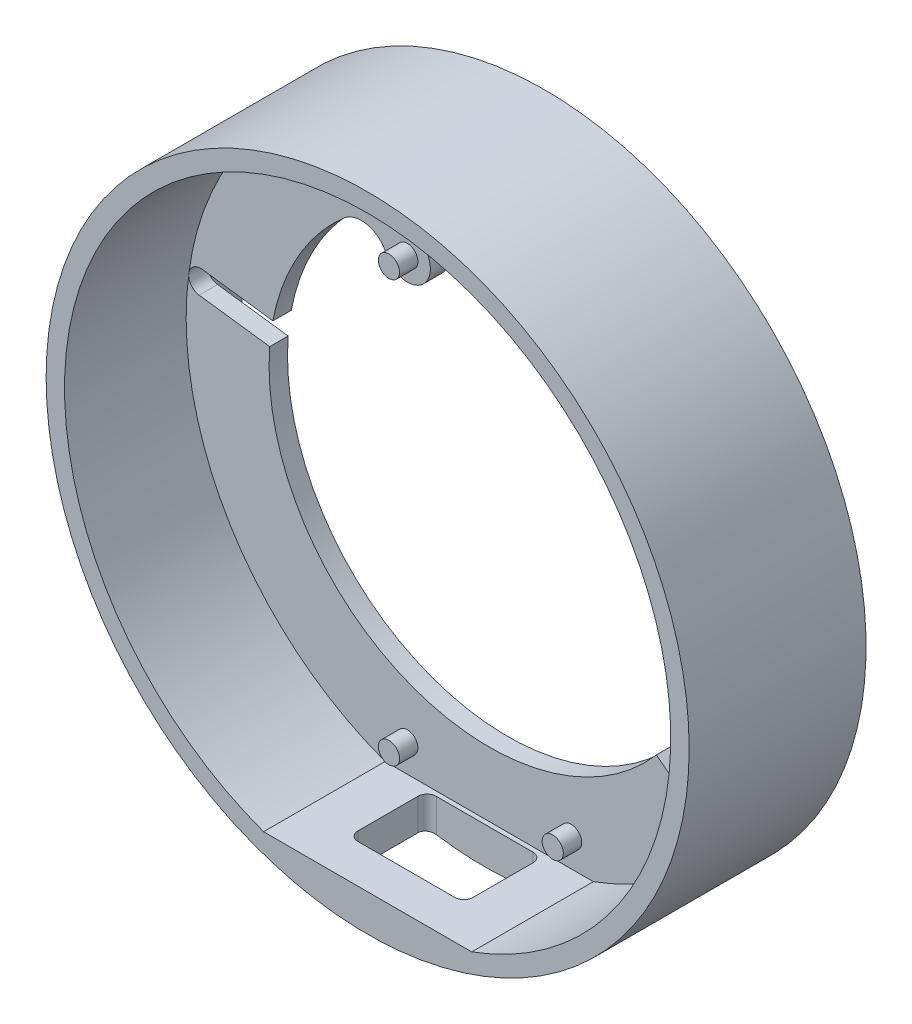
SolidWorks part; units mm, degrees
ref_plane "Plan de face" through (0, 0, 0) normal (0, 0, 1) x (1, 0, 0)
ref_plane "Plan de dessus" through (0, 0, 0) normal (0, 1, 0) x (1, 0, 0)
ref_plane "Plan de droite" through (0, 0, 0) normal (1, 0, 0) x (0, 0, -1)
sketch "Esquisse_carte_affichage" plane through (0, 0, 0) normal (0, 0, 1) x (1, 0, 0)
  circle A0 centre (19.25, 25.1) radius 0.5
  circle A1 centre (25.07, -19.23) radius 0.5
  circle A2 centre (29.18, 12.09) radius 0.5
  circle A3 centre (31.32, -4.14) radius 0.5
  circle A4 centre (-29.21, -12.07) radius 0.5
  circle A5 centre (-31.32, 4.14) radius 0.5
  circle A6 centre (-26.4935, -7.4094) radius 0.25
  circle A7 centre (-23.6728, -14.0139) radius 0.25
  circle A8 centre (-19.2392, -19.6637) radius 0.25
  circle A9 centre (-13.4943, -23.973) radius 0.25
  circle A10 centre (-6.8298, -26.6487) radius 0.25
  circle A11 centre (0.3, -27.5085) radius 0.25
  circle A12 centre (7.4094, -26.4935) radius 0.25
  circle A13 centre (14.0139, -23.6728) radius 0.25
  circle A14 centre (19.6637, -19.2392) radius 0.25
  circle A15 centre (23.973, -13.4943) radius 0.25
  circle A16 centre (26.6487, -6.8298) radius 0.25
  circle A17 centre (27.5085, 0.3) radius 0.25
  circle A18 centre (26.4935, 7.4094) radius 0.25
  circle A19 centre (23.6728, 14.0139) radius 0.25
  circle A20 centre (19.2392, 19.6637) radius 0.25
  circle A21 centre (13.4943, 23.973) radius 0.25
  circle A22 centre (6.8298, 26.6487) radius 0.25
  circle A23 centre (-0.3, 27.5085) radius 0.25
  circle A24 centre (-7.4094, 26.4935) radius 0.25
  circle A25 centre (-14.0139, 23.6728) radius 0.25
  circle A26 centre (-19.6637, 19.2392) radius 0.25
  circle A27 centre (-23.973, 13.4943) radius 0.25
  circle A28 centre (-26.6487, 6.8298) radius 0.25
  circle A29 centre (-27.5085, -0.3) radius 0.25
  circle A30 centre (-30.2, -7.1) radius 0.25
  circle A31 centre (-26.5986, -15.746) radius 0.25
  circle A32 centre (-28.1305, -7.8674) radius 0.25
  circle A33 centre (-21.6169, -22.0937) radius 0.25
  circle A34 centre (-25.1358, -14.8801) radius 0.25
  circle A35 centre (-15.162, -26.9359) radius 0.25
  circle A36 centre (-20.428, -20.8785) radius 0.25
  circle A37 centre (-7.6738, -29.9423) radius 0.25
  circle A38 centre (-14.3281, -25.4544) radius 0.25
  circle A39 centre (0.3371, -30.9082) radius 0.25
  circle A40 centre (-7.252, -28.2956) radius 0.25
  circle A41 centre (8.3254, -29.7678) radius 0.25
  circle A42 centre (0.3185, -29.2082) radius 0.25
  circle A43 centre (15.746, -26.5986) radius 0.25
  circle A44 centre (7.8674, -28.1305) radius 0.25
  circle A45 centre (22.0937, -21.6169) radius 0.25
  circle A46 centre (14.8801, -25.1358) radius 0.25
  circle A47 centre (26.9359, -15.162) radius 0.25
  circle A48 centre (20.8785, -20.428) radius 0.25
  circle A49 centre (29.9423, -7.6738) radius 0.25
  circle A50 centre (25.4544, -14.3281) radius 0.25
  circle A51 centre (30.9082, 0.3371) radius 0.25
  circle A52 centre (28.2956, -7.252) radius 0.25
  circle A53 centre (29.7678, 8.3254) radius 0.25
  circle A54 centre (29.2082, 0.3185) radius 0.25
  circle A55 centre (26.5986, 15.746) radius 0.25
  circle A56 centre (28.1305, 7.8674) radius 0.25
  circle A57 centre (21.6169, 22.0937) radius 0.25
  circle A58 centre (25.1358, 14.8801) radius 0.25
  circle A59 centre (15.162, 26.9359) radius 0.25
  circle A60 centre (20.428, 20.8785) radius 0.25
  circle A61 centre (7.6738, 29.9423) radius 0.25
  circle A62 centre (14.3281, 25.4544) radius 0.25
  circle A63 centre (-0.3371, 30.9082) radius 0.25
  circle A64 centre (7.252, 28.2956) radius 0.25
  circle A65 centre (-8.3254, 29.7678) radius 0.25
  circle A66 centre (-0.3185, 29.2082) radius 0.25
  circle A67 centre (-15.746, 26.5986) radius 0.25
  circle A68 centre (-7.8674, 28.1305) radius 0.25
  circle A69 centre (-22.0937, 21.6169) radius 0.25
  circle A70 centre (-14.8801, 25.1358) radius 0.25
  circle A71 centre (-26.9359, 15.162) radius 0.25
  circle A72 centre (-20.8785, 20.428) radius 0.25
  circle A73 centre (-29.9423, 7.6738) radius 0.25
  circle A74 centre (-25.4544, 14.3281) radius 0.25
  circle A75 centre (-30.9082, -0.3371) radius 0.25
  circle A76 centre (-28.2956, 7.252) radius 0.25
  circle A77 centre (0, 0) radius 26.162
  circle A78 centre (0, 0) radius 32.766
  dimension "D1" = 65.532
  dimension "D2" = 52.324
sketch "Esquisse_carte_mère" plane through (0, 0, 0) normal (0, 0, 1) x (1, 0, 0)
  line L0 (-11.3435, -28.5174) -> (-11.0897, -29.13)
  line L1 (-11.0897, -29.13) -> (-10.6861, -29.6561)
  line L2 (-10.6861, -29.6561) -> (-10.16, -30.0597)
  line L3 (-10.16, -30.0597) -> (-9.5474, -30.3135)
  line L4 (-9.5474, -30.3135) -> (-8.89, -30.4)
  line L5 (-8.89, -30.4) -> (-2.413, -30.4)
  line L6 (-2.413, -30.4) -> (-1.905, -29.892)
  line L7 (-1.905, -29.892) -> (1.905, -29.892)
  line L8 (1.905, -29.892) -> (2.413, -30.4)
  line L9 (2.413, -30.4) -> (8.89, -30.4)
  line L10 (8.89, -30.4) -> (9.5474, -30.3135)
  line L11 (9.5474, -30.3135) -> (10.16, -30.0597)
  line L12 (10.16, -30.0597) -> (10.6861, -29.6561)
  line L13 (10.6861, -29.6561) -> (11.0897, -29.13)
  line L14 (11.0897, -29.13) -> (11.3435, -28.5174)
  line L15 (11.3435, -28.5174) -> (11.43, -27.86)
  line L16 (11.43, -27.86) -> (11.43, 17.86)
  line L17 (11.43, 17.86) -> (11.3435, 18.5174)
  line L18 (11.3435, 18.5174) -> (11.0897, 19.13)
  line L19 (11.0897, 19.13) -> (10.6861, 19.6561)
  line L20 (10.6861, 19.6561) -> (10.16, 20.0597)
  line L21 (10.16, 20.0597) -> (9.5474, 20.3135)
  line L22 (9.5474, 20.3135) -> (8.89, 20.4)
  line L23 (8.89, 20.4) -> (-8.89, 20.4)
  line L24 (-8.89, 20.4) -> (-9.5474, 20.3135)
  line L25 (-9.5474, 20.3135) -> (-10.16, 20.0597)
  line L26 (-10.16, 20.0597) -> (-10.6861, 19.6561)
  line L27 (-10.6861, 19.6561) -> (-11.0897, 19.13)
  line L28 (-11.0897, 19.13) -> (-11.3435, 18.5174)
  line L29 (-11.3435, 18.5174) -> (-11.43, 17.86)
  line L30 (-11.43, 17.86) -> (-11.43, -27.86)
  line L31 (-11.43, -27.86) -> (-11.3435, -28.5174)
  line L32 (8.9522, -28.0199) -> (-18113.3609, 46572.2136) construction
  line L33 (-8.9266, -27.9541) -> (18113.3865, 46572.2795) construction
  circle A0 centre (-3.3, -25.05) radius 0.4
  circle A1 centre (3.3, -25.05) radius 0.4
  circle A2 centre (-3.6, -27.86) radius 0.45
  circle A3 centre (3.6, -27.86) radius 0.45
  circle A4 centre (10.16, 14.05) radius 0.5
  circle A5 centre (10.16, 11.51) radius 0.5
  circle A6 centre (10.16, 8.97) radius 0.5
  circle A7 centre (10.16, 6.43) radius 0.5
  circle A8 centre (10.16, 3.89) radius 0.5
  circle A9 centre (10.16, 1.35) radius 0.5
  circle A10 centre (10.16, -1.19) radius 0.5
  circle A11 centre (10.16, -3.73) radius 0.5
  circle A12 centre (10.16, -6.27) radius 0.5
  circle A13 centre (10.16, -8.81) radius 0.5
  circle A14 centre (10.16, -11.35) radius 0.5
  circle A15 centre (10.16, -13.89) radius 0.5
  circle A16 centre (-10.16, -24.05) radius 0.5
  circle A17 centre (-10.16, -21.51) radius 0.5
  circle A18 centre (-10.16, -18.97) radius 0.5
  circle A19 centre (-10.16, -16.43) radius 0.5
  circle A20 centre (-10.16, -13.89) radius 0.5
  circle A21 centre (-10.16, -11.35) radius 0.5
  circle A22 centre (-10.16, -8.81) radius 0.5
  circle A23 centre (-10.16, -6.27) radius 0.5
  circle A24 centre (-10.16, -3.73) radius 0.5
  circle A25 centre (-10.16, -1.19) radius 0.5
  circle A26 centre (-10.16, 1.35) radius 0.5
  circle A27 centre (-10.16, 3.89) radius 0.5
  circle A28 centre (-10.16, 6.43) radius 0.5
  circle A29 centre (-10.16, 8.97) radius 0.5
  circle A30 centre (-10.16, 11.51) radius 0.5
  circle A31 centre (-10.16, 14.05) radius 0.5
  circle A32 centre (-8.89, -27.86) radius 1.25
  circle A33 centre (8.89, -27.86) radius 1.25
  circle A34 centre (-8.89, 17.86) radius 1.25
  circle A35 centre (8.89, 17.86) radius 1.25
  circle A36 centre (-1.95, -25.955) radius 0.35
  circle A37 centre (1.95, -25.955) radius 0.35
  circle A38 centre (-2.2, 15.706) radius 0.45
  circle A39 centre (3.048, -15.795) radius 0.25
  circle A40 centre (1.016, -20.875) radius 0.25
  circle A41 centre (-6.223, -9.826) radius 0.25
  circle A42 centre (-6.096, -16.43) radius 0.25
  circle A43 centre (7.3914, -2.0028) radius 0.25
  circle A44 centre (7.366, -18.462) radius 0.25
  circle A45 centre (-1.905, 12.018) radius 0.25
  circle A46 centre (1.905, 9.224) radius 0.25
  circle A47 centre (-5.715, -21.129) radius 0.25
  circle A48 centre (-4.064, -1.571) radius 0.25
  circle A49 centre (-8.509, -22.78) radius 0.25
  circle A50 centre (0.2286, -14.5758) radius 0.25
  circle A51 centre (0.508, 7.446) radius 0.25
  circle A52 centre (0.635, 8.589) radius 0.25
  circle A53 centre (-7.112, 0.334) radius 0.25
  circle A54 centre (4.953, -15.795) radius 0.25
  circle A55 centre (0, 10.494) radius 0.25
  circle A56 centre (-4.191, -16.43) radius 0.25
  circle A57 centre (-0.889, -17.573) radius 0.25
  circle A58 centre (5.842, -10.715) radius 0.25
  circle A59 centre (2.159, -17.446) radius 0.25
  circle A60 centre (0, -27.987) radius 0.25
  circle A61 centre (-1.397, 4.271) radius 0.25
  circle A62 centre (-5.207, 1.985) radius 0.25
  circle A63 centre (-0.381, -6.651) radius 0.25
  circle A64 centre (6.858, 8.462) radius 0.25
  circle A65 centre (5.207, 3.128) radius 0.25
  circle A66 centre (2.667, 4.525) radius 0.25
  circle A67 centre (5.08, 11.764) radius 0.25
  circle A68 centre (0, 14.431) radius 0.25
  circle A69 centre (-1.778, 8.716) radius 0.25
  circle A70 centre (-2.921, 4.271) radius 0.25
  circle A71 centre (-5.588, 3.128) radius 0.25
  circle A72 centre (-1.905, -19.732) radius 0.25
  circle A73 centre (-5.842, -8.683) radius 0.25
  circle A74 centre (-3.048, -20.113) radius 0.25
  circle A75 centre (-6.604, -7.667) radius 0.25
  circle A76 centre (-5.207, -10.842) radius 0.25
  circle A77 centre (10.668, -26.082) radius 0.25
  circle A78 centre (5.969, -4.365) radius 0.25
  circle A79 centre (5.08, -9.191) radius 0.25
  circle A80 centre (-3.81, -3.349) radius 0.25
  circle A81 centre (-4.953, -9.699) radius 0.25
  circle A82 centre (3.048, 6.43) radius 0.25
  circle A83 centre (5.969, -3.222) radius 0.25
  circle A84 centre (6.858, -7.667) radius 0.25
  circle A85 centre (6.477, 6.303) radius 0.25
  circle A86 centre (-1.27, 10.367) radius 0.25
  circle A87 centre (-1.0922, -0.1994) radius 0.25
  circle A88 centre (0.508, -0.428) radius 0.25
  circle A89 centre (4.318, -17.065) radius 0.25
  circle A90 centre (1.524, 4.144) radius 0.25
  circle A91 centre (-2.921, -1.444) radius 0.25
  circle A92 centre (3.302, -10.08) radius 0.25
  circle A93 centre (-3.81, -10.08) radius 0.25
  circle A94 centre (-5.08, -6.778) radius 0.25
  point P222 (0, -5)
  dimension "D5" = 2.5
  dimension "D1" = 2.54
  dimension "D2" = 2.54
  dimension "D3" = 2.54
  dimension "D4" = 2.54
sketch "Esquisse_support" plane through (0, 0, 0) normal (0, 0, 1) x (1, 0, 0)
  line L0 (0, 0) -> (0, -50000) construction
  line L1 (0, 0) -> (-31.32, 4.14) construction
  line L2 (0, 0) -> (19.25, 25.1) construction
  line L3 (0, 0) -> (25.07, -19.23) construction
  line L4 (25.07, -19.23) -> (30456.2807, 39653.7005) construction
  line L5 (19.25, 25.1) -> (39694.4792, -30403.1136) construction
  line L6 (-31.32, 4.14) -> (6520.8813, 49572.9675) construction
  line L7 (-31.1487, 5.4363) -> (-23.4871, 4.4235)
  line L8 (-31.4913, 2.8437) -> (-23.8298, 1.831)
  line L9 (18.2437, 25.8718) -> (13.5179, 19.7098)
  line L10 (20.2563, 24.3282) -> (15.5305, 18.1663)
  line L11 (25.8637, -18.1952) -> (19.7291, -13.4897)
  line L12 (24.2763, -20.2648) -> (18.1417, -15.5592)
  line L13 (-8.89, 17.86) -> (46591.3436, 18140.1731) construction
  line L14 (8.89, 17.86) -> (-46591.3436, 18140.1731) construction
  line L15 (11.22, 16.9539) -> (13.5179, 19.7098)
  line L16 (72498.2044, -186428.9542) -> (-90602.6131, 232973.148) construction
  line L17 (-72498.1788, -186428.8884) -> (90602.6387, 232973.2138) construction
  circle A0 centre (0, 0) radius 32.9 construction
  circle A1 centre (0, 0) radius 34.9
  arc A2 (-32.6163, 4.3113) -> (-31.4913, 2.8437) centre (-31.32, 4.14) ccw
  arc A3 (-32.6163, 4.3113) -> (-31.1487, 5.4363) centre (-31.32, 4.14) cw
  arc A4 (20.0218, 26.1063) -> (18.2437, 25.8718) centre (19.25, 25.1) ccw
  arc A5 (20.0218, 26.1063) -> (20.2563, 24.3282) centre (19.25, 25.1) cw
  arc A6 (26.1048, -20.0237) -> (25.8637, -18.1952) centre (25.07, -19.23) ccw
  arc A7 (26.1048, -20.0237) -> (24.2763, -20.2648) centre (25.07, -19.23) cw
  arc A8 (-23.4871, 4.4235) -> (13.5179, 19.7098) centre (0, 0) cw construction
  arc A9 (-23.8298, 1.831) -> (18.1417, -15.5592) centre (0, 0) ccw
  arc A10 (19.7291, -13.4897) -> (15.5305, 18.1663) centre (0, 0) ccw
  arc A11 (-6.56, 18.7661) -> (-11.22, 16.9539) centre (-8.89, 17.86) cw
  arc A12 (6.56, 18.7661) -> (11.22, 16.9539) centre (8.89, 17.86) ccw
  arc A13 (-6.56, 18.7661) -> (-4.1838, 23.531) centre (-3.28, 20.1053) cw
  arc A14 (6.56, 18.7661) -> (4.1838, 23.531) centre (3.28, 20.1053) ccw
  arc A15 (-11.22, 16.9539) -> (-15.8818, 17.86) centre (-13.8724, 15.7529) ccw
  arc A16 (-23.4871, 4.4235) -> (-15.8818, 17.86) centre (0, 0) cw
  arc A17 (-4.1838, 23.531) -> (4.1838, 23.531) centre (0, 0) cw
  point P37 (-4.1838, 23.531)
  dimension "D1" = 65.8
  dimension "D2" = 69.8
  dimension "D12" = 2.5
  dimension "D13" = 2.5
  dimension "D3" = 90
  dimension "D4" = 90
  dimension "D5" = 90
  dimension "D7" = 90
  dimension "D8" = 90
  dimension "D9" = 90
  dimension "D10" = 90
  dimension "D11" = 90
extrude "Boss.-Extru.1" add sketch "Esquisse_support" along normal blind 2 contours A1 A13 A17 A14 A12 L15 L9 A4 A5 L10 A10 L11 A6 A7 L12 A9 L8 A2 A3 L7 A16 A15 A11 region at (-33.9129, 0, 0)
sketch "Esquisse6" plane through (0, 0, 2) normal (0, 0, 1) x (1, 0, 0)
  line L0 (0, 0) -> (0, -50000) construction
  circle A0 centre (-8.89, 17.86) radius 1.15
  circle A1 centre (-8.89, -27.86) radius 1.15
  circle A2 centre (8.89, -27.86) radius 1.15
  circle A3 centre (8.89, 17.86) radius 1.15
  dimension "D1" = 2.3
  dimension "D2" = 2.3
extrude "Boss.-Extru.2" add sketch "Esquisse6" along normal blind 2
sketch "Esquisse7" plane through (0, 0, 0) normal (0, 0, -1) x (-1, 0, 0)
  circle A0 centre (0, 0) radius 34.9
  circle A1 centre (0, 0) radius 32.9
extrude "Boss.-Extru.3" add sketch "Esquisse7" along normal blind 4
sketch "Esquisse8" plane through (0, 0, 2) normal (0, 0, 1) x (1, 0, 0)
  line L0 (0, 0) -> (0, -50000) construction
  line L1 (-11.296, -30.9) -> (11.296, -30.9)
  line L2 (-8.89, -30.4) -> (-2.413, -30.4) construction
  circle A0 centre (0, 0) radius 34.9
  circle A1 centre (0, 0) radius 32.9 construction
  arc A2 (-11.296, -30.9) -> (11.296, -30.9) centre (0, 0) cw
  point P9 (0, -30.9)
  circle M5 centre (0, 0) radius 34.9
  dimension "D2" = 0.5
extrude "Boss.-Extru.5" add sketch "Esquisse8" along normal blind 13.2 contours A2 L1 M5 region at (-33.9129, 0, 2)
sketch "Ouverture_USB" plane through (0, -30.9, 0) normal (0, 1, 0) x (1, 0, 0)
  line L0 (0, -16.2747) -> (0, 5.3613) construction
  line L2 (-5.25, -11) -> (5.25, -11)
  line L3 (-6.25, -10) -> (-6.25, -3.5)
  line L4 (-5.25, -2.5) -> (5.25, -2.5)
  line L5 (6.25, -10) -> (6.25, -3.5)
  arc A0 (6.25, -10) -> (5.25, -11) centre (5.25, -10) cw
  arc A1 (6.25, -3.5) -> (5.25, -2.5) centre (5.25, -3.5) ccw
  arc A2 (-5.25, -2.5) -> (-6.25, -3.5) centre (-5.25, -3.5) ccw
  arc A3 (-6.25, -10) -> (-5.25, -11) centre (-5.25, -10) ccw
  dimension "D4" = 1
  dimension "D1" = 8.5
  dimension "D2" = 12.5
  dimension "D3" = 2.5
extrude "Enlèv. mat.-Extru.1" cut sketch "Ouverture_USB" against normal blind 10
sketch "Esquisse10" plane through (0, 0, 15.2) normal (0, 0, 1) x (1, 0, 0)
  circle A0 centre (0, 0) radius 34.9
